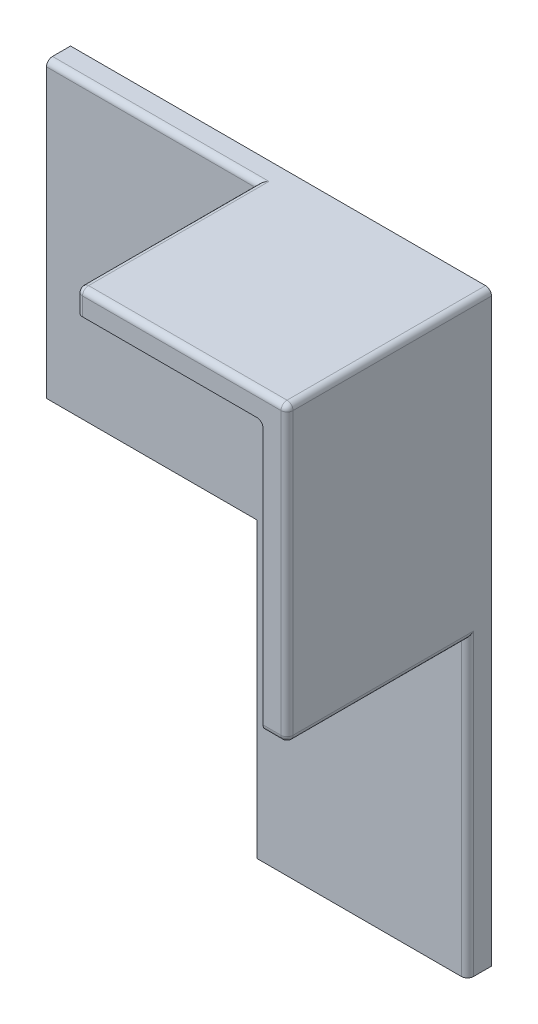
SolidWorks part; units mm, degrees
ref_plane "정면" through (0, 0, 0) normal (0, 0, 1) x (1, 0, 0)
ref_plane "윗면" through (0, 0, 0) normal (0, 1, 0) x (1, 0, 0)
ref_plane "우측면" through (0, 0, 0) normal (1, 0, 0) x (0, 0, -1)
sketch "스케치1" plane through (0, 0, 0) normal (0, 0, 1) x (1, 0, 0)
  line L1 (44.7488, 110.1527) -> (114.7488, 110.1527)
  line L2 (44.7488, 12.6527) -> (44.7488, -84.8473)
  line L3 (44.7488, -84.8473) -> (114.7488, -84.8473)
  line L4 (114.7488, 110.1527) -> (114.7488, -84.8473)
  line L5 (114.7488, 110.1527) -> (-25.2512, 110.1527)
  line L6 (114.7488, 110.1527) -> (114.7488, 12.6527)
  line L7 (44.7488, 12.6527) -> (-25.2512, 12.6527)
  line L8 (-25.2512, 110.1527) -> (-25.2512, 12.6527)
  dimension "D1" = 195
  dimension "D2" = 140
  dimension "D3" = 70
  dimension "D4" = 97.5
extrude "보스-돌출1" add sketch "스케치1" along normal blind 8 contours L5 L8 L7 L2 L3 L4 L1 region at (56.4155, 28.9027, 0)
sketch "스케치3" plane through (0, 0, 0) normal (0, 0, 1) x (1, 0, 0)
  line L0 (114.7488, 110.1527) -> (-25.2512, 110.1527) construction
  line L1 (104.2488, 103.1516) -> (105.9988, 100.1205)
  line L2 (105.9988, 100.1205) -> (109.4988, 100.1205)
  line L3 (109.4988, 100.1205) -> (111.2488, 103.1516)
  line L4 (111.2488, 103.1516) -> (109.4988, 106.1827)
  line L5 (109.4988, 106.1827) -> (105.9988, 106.1827)
  line L6 (105.9988, 106.1827) -> (104.2488, 103.1516)
  line L7 (114.7488, 110.1527) -> (114.7488, -84.8473) construction
  line L8 (44.7488, 12.6527) -> (-25.2512, 12.6527) construction
  line L9 (-21.7512, 82.1516) -> (-20.0012, 79.1205)
  line L10 (-20.0012, 79.1205) -> (-16.5012, 79.1205)
  line L11 (-16.5012, 79.1205) -> (-14.7512, 82.1516)
  line L12 (-14.7512, 82.1516) -> (-16.5012, 85.1827)
  line L13 (-16.5012, 85.1827) -> (-20.0012, 85.1827)
  line L14 (-20.0012, 85.1827) -> (-21.7512, 82.1516)
  line L15 (-21.7512, 21.6538) -> (-20.0012, 18.6227)
  line L16 (-20.0012, 18.6227) -> (-16.5012, 18.6227)
  line L17 (-16.5012, 18.6227) -> (-14.7512, 21.6538)
  line L18 (-14.7512, 21.6538) -> (-16.5012, 24.6848)
  line L19 (-16.5012, 24.6848) -> (-20.0012, 24.6848)
  line L20 (-20.0012, 24.6848) -> (-21.7512, 21.6538)
  line L21 (57.9988, 100.1205) -> (61.4988, 100.1205)
  line L22 (61.4988, 100.1205) -> (63.2488, 103.1516)
  line L23 (63.2488, 103.1516) -> (61.4988, 106.1827)
  line L24 (61.4988, 106.1827) -> (57.9988, 106.1827)
  line L25 (57.9988, 106.1827) -> (56.2488, 103.1516)
  line L26 (56.2488, 103.1516) -> (57.9988, 100.1205)
  line L27 (57.9988, 93.1805) -> (56.2488, 90.1494)
  line L28 (56.2488, 90.1494) -> (57.9988, 87.1183)
  line L29 (57.9988, 87.1183) -> (61.4988, 87.1183)
  line L30 (61.4988, 87.1183) -> (63.2488, 90.1494)
  line L31 (63.2488, 90.1494) -> (61.4988, 93.1805)
  line L32 (61.4988, 93.1805) -> (57.9988, 93.1805)
  line L33 (104.7488, -77.8462) -> (106.4988, -80.8773)
  line L34 (109.4988, 18.6205) -> (111.2488, 21.6516)
  line L35 (111.2488, 21.6516) -> (109.4988, 24.6827)
  line L36 (109.4988, 24.6827) -> (105.9988, 24.6827)
  line L37 (105.9988, 24.6827) -> (104.2488, 21.6516)
  line L38 (104.2488, 21.6516) -> (105.9988, 18.6205)
  line L39 (105.9988, 18.6205) -> (109.4988, 18.6205)
  line L40 (106.4988, -80.8773) -> (109.9988, -80.8773)
  line L41 (109.9988, -80.8773) -> (111.7488, -77.8462)
  line L42 (111.7488, -77.8462) -> (109.9988, -74.8152)
  line L43 (109.9988, -74.8152) -> (106.4988, -74.8152)
  line L44 (106.4988, -74.8152) -> (104.7488, -77.8462)
  line L46 (44.7488, -84.8473) -> (114.7488, -84.8473) construction
  line L47 (-25.2512, 110.1527) -> (-25.2512, 12.6527) construction
  circle A0 centre (107.7488, 103.1516) radius 3.0311 construction
  circle A1 centre (-18.2512, 82.1516) radius 3.5 construction
  circle A2 centre (-18.2512, 21.6538) radius 3.5 construction
  circle A3 centre (59.7488, 103.1516) radius 3.5 construction
  circle A4 centre (59.7488, 90.1494) radius 3.5 construction
  circle A5 centre (107.7488, 21.6516) radius 3.5 construction
  circle A6 centre (108.2488, -77.8462) radius 3.5 construction
  dimension "D5" = 7
  dimension "D8" = 7
  dimension "D11" = 7
  dimension "D14" = 7
  dimension "D17" = 7
  dimension "D20" = 7
  dimension "D1" = 7
  dimension "D2" = 3.97
  dimension "D3" = 3.5
  dimension "D4" = 3.5
  dimension "D6" = 24.97
  dimension "D7" = 3.5
  dimension "D9" = 5.97
  dimension "D10" = 3.5
  dimension "D12" = 3.97
  dimension "D13" = 81.5
  dimension "D15" = 6.94
  dimension "D16" = 81.5
  dimension "D18" = 3.5
  dimension "D19" = 85.47
  dimension "D21" = 3
  dimension "D22" = 3.97
extrude "컷-돌출2" cut sketch "스케치3" along normal blind 2 and the other way through all
sketch "스케치4" plane through (0, 0, 2) normal (0, 0, -1) x (-1, 0, 0)
  line L0 (-61.4988, 106.1827) -> (-57.9988, 106.1827) construction
  line L1 (-57.9988, 100.1205) -> (-61.4988, 100.1205) construction
  line L2 (-61.4988, 93.1805) -> (-57.9988, 93.1805) construction
  line L3 (-106.4988, -80.8773) -> (-109.9988, -80.8773) construction
  line L4 (-104.2488, 103.1516) -> (-105.9988, 100.1205) construction
  line L5 (-109.4988, 106.1827) -> (-105.9988, 106.1827) construction
  line L6 (-109.4988, 24.6827) -> (-105.9988, 24.6827) construction
  line L7 (-105.9988, 24.6827) -> (-104.2488, 21.6516) construction
  line L8 (-109.4988, 18.6205) -> (-111.2488, 21.6516) construction
  line L9 (-106.4988, -74.8152) -> (-104.7488, -77.8462) construction
  line L10 (20.0012, 79.1205) -> (16.5012, 79.1205) construction
  line L11 (20.0012, 85.1827) -> (21.7512, 82.1516) construction
  line L12 (16.5012, 79.1205) -> (14.7512, 82.1516) construction
  line L13 (21.7512, 21.6538) -> (20.0012, 18.6227) construction
  line L14 (20.0012, 24.6848) -> (21.7512, 21.6538) construction
  circle A0 centre (-59.7705, 103.1527) radius 2
  circle A1 centre (-59.7705, 90.1494) radius 2
  circle A2 centre (-107.7592, 103.1527) radius 2
  circle A3 centre (-108.2481, -77.8453) radius 2
  circle A4 centre (-107.7482, 21.6527) radius 2
  circle A5 centre (18.2525, 21.6538) radius 2
  circle A6 centre (18.2531, 82.1505) radius 2
  dimension "D1" = 4
  dimension "D4" = 4
  dimension "D7" = 4
  dimension "D9" = 4
  dimension "D13" = 4
  dimension "D16" = 4
  dimension "D20" = 4
  dimension "D2" = 3.03
  dimension "D3" = 3.0322
  dimension "D5" = 3.0311
  dimension "D6" = 6.0622
  dimension "D8" = 3.03
  dimension "D10" = 3.03
  dimension "D11" = 3.03
  dimension "D12" = 3.0322
  dimension "D14" = 3.03
  dimension "D15" = 3.032
  dimension "D17" = 3.03
  dimension "D18" = 3.03
  dimension "D19" = 3.0322
  dimension "D21" = 3.03
  dimension "D22" = 3.03
  dimension "D23" = 3.5104
extrude "컷-돌출7" cut sketch "스케치4" against normal blind 5
sketch "스케치5" plane through (0, 0, 8) normal (0, 0, 1) x (1, 0, 0)
  line L0 (114.7488, 110.1527) -> (114.7488, -84.8473) construction
  line L1 (114.7488, 110.1527) -> (44.7488, 110.1527)
  line L2 (114.7488, 110.1527) -> (114.7488, 102.1527)
  line L3 (114.7488, 102.1527) -> (44.7488, 102.1527)
  line L4 (44.7488, 110.1527) -> (44.7488, 102.1527)
  line L5 (106.7488, 102.1527) -> (114.7488, 102.1527)
  line L6 (106.7488, 102.1527) -> (106.7488, 12.6527)
  line L7 (106.7488, 12.6527) -> (114.7488, 12.6527)
  line L8 (114.7488, 102.1527) -> (114.7488, 12.6527)
  line M8 (114.7488, -84.8473) -> (114.7488, 110.1527)
  dimension "D1" = 8
  dimension "D2" = 8
  dimension "D3" = 70
  dimension "D4" = 97.5
extrude "보스-돌출3" add sketch "스케치5" along normal blind 60 contours L6 L7 L3 M8 | L2 L1 L4 L3 region at (110.7488, 57.4027, 8)
fillet "필렛1" radius 2 7 edges at (114.7488, -36.0973, 8) (9.7488, 110.1527, 8) (44.7488, 110.1527, 38) (114.7488, 12.6527, 38) (79.7488, 110.1527, 68) (114.7488, 61.4027, 68) (114.7488, 110.1527, 34)
fillet "필렛2" radius 2 4 edges at (114.163, 13.2385, 67.4142) (45.3346, 109.5669, 67.4142) (109.7488, 12.6527, 68) (44.7488, 105.1527, 68)
fillet "필렛3" radius 2 1 edges at (106.7488, 102.1527, 38)
ref_plane "평면1" through (-35.2512, 0, 0) normal (-1, 0, 0) x (0, 0, 1)
